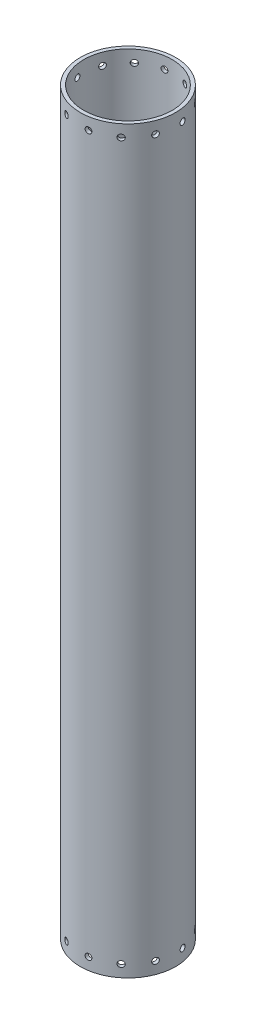
SolidWorks part; units mm, degrees
material "6061-T6 (SS)"
ref_plane "Front Plane" through (0, 0, 0) normal (0, 0, 1) x (1, 0, 0)
ref_plane "Top Plane" through (0, 0, 0) normal (0, 1, 0) x (1, 0, 0)
ref_plane "Right Plane" through (0, 0, 0) normal (1, 0, 0) x (0, 0, -1)
sketch "Sketch1" plane through (0, 0, 0) normal (0, 1, 0) x (1, 0, 0)
  circle A0 centre (0, 0) radius 63.5
  circle A1 centre (0, 0) radius 58.7375
  point P5 (0, 0)
extrude "Boss-Extrude1" add sketch "Sketch1" along normal blind 984.25
sketch3d "3DSketch2"
  circle A0 centre (0, 968.375, 0) radius 63.5
  circle A1 centre (0, 968.375, 0) radius 63.5
  point P2 (0, 904.875, 0)
  point P4 (0, 904.875, 0)
  dimension "D1" = 15.875
sketch3d "3DSketch3"
  line L0 (22.6176, 0, -59.3354) -> (22.6176, 984.25, -59.3354)
  circle A0 centre (0, 15.875, 0) radius 63.5
  circle A1 centre (0, 15.875, 0) radius 63.5
  circle A2 centre (0, 0, 0) radius 63.5 construction
  circle A3 centre (0, 984.25, 0) radius 63.5 construction
  point P2 (0, 79.375, 0)
  point P4 (0, 79.375, 0)
  point P9 (0, 63.5, 0)
  point P12 (0, 1047.75, 0)
  dimension "D1" = 15.875
hole_wizard "5/16 (0.3125) Diameter Hole1" positions "3DSketch1" profile "Sketch2" hole size "5/16" standard "ANSI Inch" end condition up to next
sketch3d "3DSketch1"
  line L0 (22.6176, 0, -59.3354) -> (22.6176, 984.25, -59.3354) construction
  circle A0 centre (0, 968.375, 0) radius 63.5 construction
  circle A1 centre (0, 15.875, 0) radius 63.5 construction
  point P0 (22.6176, 968.375, -59.3354)
  point P6 (0, 904.875, 0)
  point P7 (22.6176, 15.875, -59.3354)
  point P13 (0, 79.375, 0)
sketch "Sketch2" plane through (22.6176, 968.375, -59.3354) normal (0, 1, 0) x (-0.9344, 0, -0.3562)
  line L0 (0, 0) -> (0, 4.7625)
  line L1 (0, 4.7625) -> (3.9687, 4.7625)
  line L2 (3.9687, 4.7625) -> (3.9687, 0)
  line L5 (3.9687, 0) -> (0, 0)
  line L11 (0, -6.35) -> (0, 107.95) construction
  dimension "Thru Hole Dia." = 7.9375
  dimension "Thru Hole Depth" = 4.7625
pattern_circular "CirPattern1" count 12 over 360 about axis through (0, 984.25, 0) along (0, 1, 0) of "5/16 (0.3125) Diameter Hole1"
sketch "Sketch3" plane through (0, 984.25, 0) normal (0, 1, 0) x (1, 0, 0)
  point P0 (0, 0)
